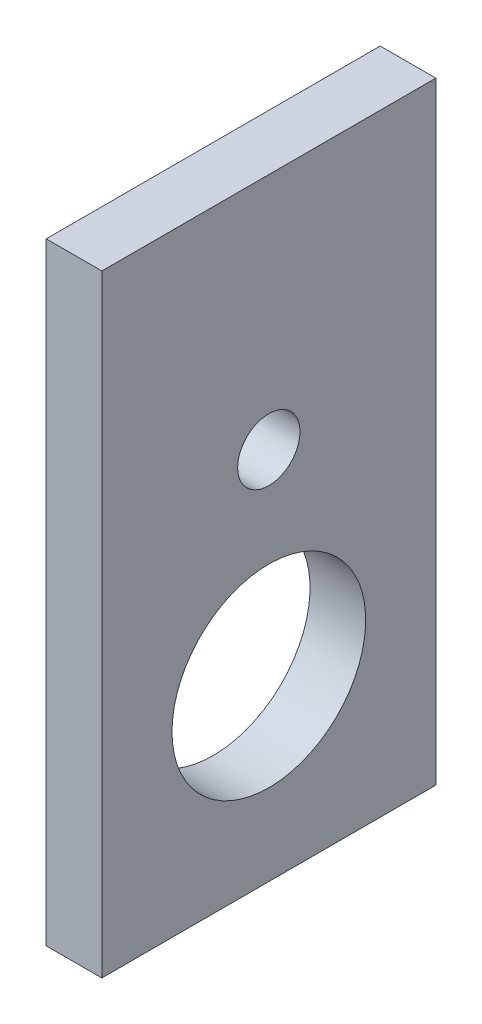
SolidWorks part; units mm, degrees
ref_plane "Front Plane" through (0, 0, 0) normal (0, 0, 1) x (1, 0, 0)
ref_plane "Top Plane" through (0, 0, 0) normal (0, 1, 0) x (1, 0, 0)
ref_plane "Right Plane" through (0, 0, 0) normal (1, 0, 0) x (0, 0, -1)
sketch "Sketch1" plane through (0, 0, 0) normal (0, 0, 1) x (1, 0, 0)
  line L0 (0, 0) -> (0, 76.2)
  line L5 (0, 76.2) -> (88.098, 76.2)
  line L6 (88.098, 76.2) -> (88.098, 101.6)
  line L7 (0, 0) -> (6.35, 0)
  line L8 (6.35, 0) -> (6.35, 76.2)
  line L9 (6.35, 76.2) -> (6.35, 69.85)
  line L10 (6.35, 69.85) -> (101.1141, 69.85)
  line L11 (88.098, 101.6) -> (94.448, 101.6)
  line L12 (94.448, 101.6) -> (94.448, 69.85)
  dimension "D1" = 25.4
  dimension "D2" = 76.2
extrude "Boss-Extrude1" add sketch "Sketch1" along normal blind 38.1 contours L7 L8 L5 L0 | L12 L11 L6 L5 L8 L10 region at (3.175, 38.1, 0) region at (47.224, 75.2636, 0)
sketch "Sketch2" plane through (0, 0, 0) normal (-1, 0, 0) x (0, 0, 1)
  line L0 (19.05, 20.32) -> (19.05, 42.672)
  line L1 (0, 0) -> (0, 76.2) construction
  line L2 (38.1, 0) -> (0, 0)
  line L3 (38.1, 0) -> (38.1, 50.8)
  line L4 (38.1, 50.8) -> (0, 50.8)
  line L5 (0, 0) -> (0, 50.8)
  line L6 (38.1, 0) -> (38.1, 20.32)
  line L7 (38.1, 20.32) -> (0, 20.32)
  circle A0 centre (19.05, 20.32) radius 11.049
  circle A1 centre (19.05, 42.672) radius 3.556
  point P13 (19.05, 20.32)
  dimension "D1" = 22.352
  dimension "D2" = 20.32
extrude "Cut-Extrude1" cut sketch "Sketch2" against normal blind 6.35 contours A0
extrude "Cut-Extrude2" cut sketch "Sketch2<4>" against normal blind 6.35 contours A1
sketch "Sketch2<4>" plane through (0, 0, 0) normal (-1, 0, 0) x (0, 0, 1) same geometry as "Sketch2"
sketch "Sketch4" plane through (0, 0, 38.1) normal (0, 0, 1) x (1, 0, 0)
  line L0 (0, 0) -> (0, 76.2) construction
  line L13 (94.448, 101.6) -> (0, 101.6)
  line L14 (94.448, 101.6) -> (94.448, 69.85)
  line L15 (94.448, 69.85) -> (0, 69.85)
  line L16 (0, 101.6) -> (0, 69.85)
extrude "Cut-Extrude5" cut sketch "Sketch4" against normal blind 76.2
